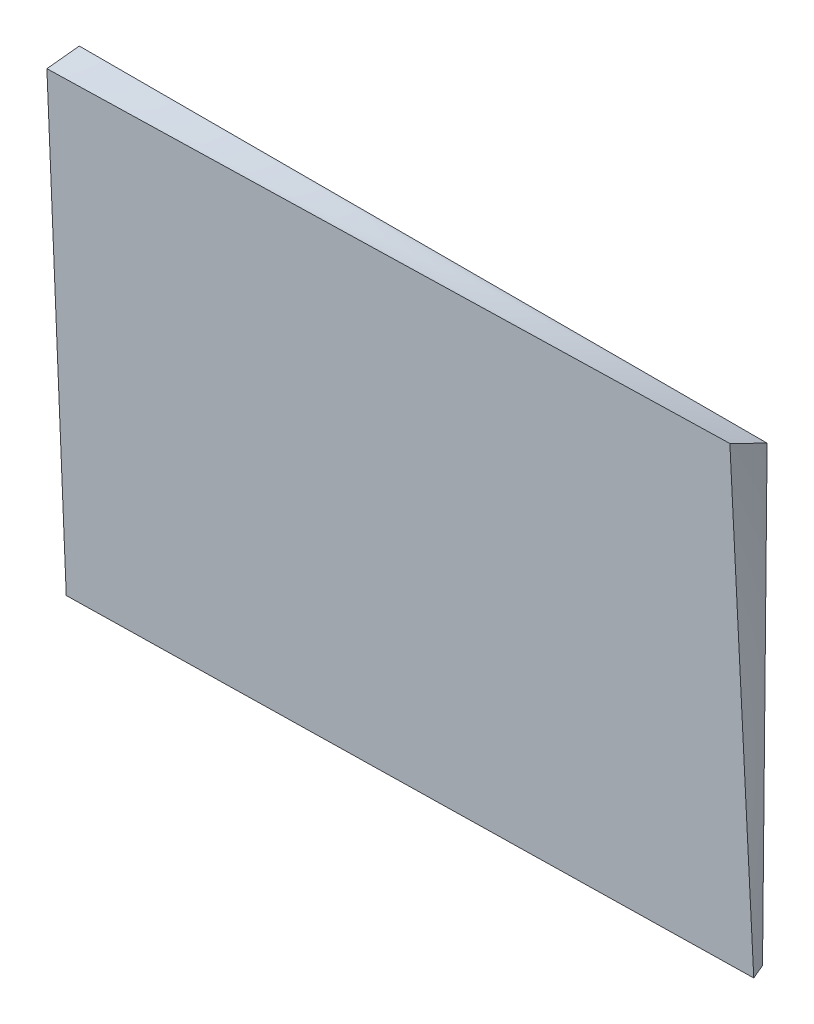
SolidWorks part; units mm, degrees
ref_plane "Ebene vorne" through (0, 0, 0) normal (0, 0, 1) x (1, 0, 0)
ref_plane "Ebene oben" through (0, 0, 0) normal (0, 1, 0) x (1, 0, 0)
ref_plane "Ebene rechts" through (0, 0, 0) normal (1, 0, 0) x (0, 0, -1)
other "Massenmittelpunkt"
sketch "Skizze1" plane through (0, 0, 0) normal (0, 0, 1) x (1, 0, 0)
  line L0 (-14.9998, 9.9997) -> (-14.9998, -10.1003)
  line L1 (-14.9998, -10.1003) -> (14.8995, -9.8992)
  line L2 (14.8995, -9.8992) -> (15.1002, 9.9997)
  line L3 (15.1002, 9.9997) -> (-14.9998, 9.9997)
  line L4 (-14.9998, -0.0503) -> (14.9998, 0.0503) construction
  line L5 (0.0502, 9.9997) -> (-0.0502, -9.9997) construction
  point P3 (0.0502, 9.9997)
  point P5 (14.9998, 0.0503)
  point P6 (-0.0502, -9.9997)
  point P7 (-14.9998, -0.0503)
  point P12 (0, 0)
  dimension "D1" = 30.1
  dimension "D2" = 29.9
  dimension "D3" = 20.1
  dimension "D4" = 19.9
  dimension "D5" = 90
ref_axis "Achse1" through (11, 0, 0) along (-1, 0, 0)
ref_plane "Rotation_Plane" through (0, 0, 0) normal (0, 0.0175, -0.9998) x (-1, 0, 0)
ref_plane "Top_Plane" through (0, -0.0175, 0.9998) normal (0, 0.0175, -0.9998) x (-1, 0, 0)
sketch "Skizze2" plane through (0, -0.0175, 0.9998) normal (0, 0.0175, -0.9998) x (-1, 0, 0)
  line L0 (15.2488, 9.6195) -> (14.7486, -10.2742)
  line L1 (14.7486, -10.2742) -> (-15.3463, -9.7166)
  line L2 (-15.3463, -9.7166) -> (-14.6512, 10.3714)
  line L3 (-14.6512, 10.3714) -> (15.2488, 9.6195)
  line L4 (0.2988, 9.9954) -> (-0.2988, -9.9954) construction
  line L5 (14.9987, -0.3274) -> (-14.9987, 0.3274) construction
  line L6 (-0.0502, 9.9982) -> (0.0502, -9.9982) construction
  line L7 (-0.0502, 9.9982) -> (0.0502, -9.9982) construction
  point P0 (0, 0)
  point P6 (0.2988, 9.9954)
  point P7 (-14.9987, 0.3274)
  point P8 (-0.2988, -9.9954)
  point P9 (14.9987, -0.3274)
  point P14 (0, 0)
  dimension "D5" = 90
  dimension "D1" = 19.9
  dimension "D2" = 20.1
  dimension "D3" = 29.9
  dimension "D4" = 30.1
  dimension "D6" = 2
loft "Ausformung2" add profiles "Skizze1", "Skizze2" connector at (-14.9998, -10.1003, 0) connector at (-14.7486, -10.2901, 0.8205)
ref_point "SWASI_Vision_Point_1_T"
ref_point "SWASI_Vision_Point_1_B"
ref_point "SWASI_Vision_Point_2_T"
ref_point "SWASI_Vision_Point_2_B"
ref_point "SWASI_Vision_Point_3_T"
ref_point "SWASI_Vision_Point_3_B"
ref_point "SWASI_Vision_Point_4_T"
ref_point "SWASI_Vision_Point_4_B"
sketch "Skizze3" plane through (0, -0.0175, 0.9998) normal (0, -0.0175, 0.9998) x (1, 0, 0)
  line L0 (-14.9987, -0.3274) -> (14.9987, 0.3274) construction
  line L1 (-0.2988, 9.9954) -> (0.2988, -9.9954) construction
  line L3 (-14, -9) -> (14, -9)
  line L4 (14.6512, 10.3714) -> (-15.2488, 9.6195)
  line L5 (-15.2488, 9.6195) -> (-14.7486, -10.2742)
  line L6 (-14.7486, -10.2742) -> (15.3463, -9.7166)
  line L7 (15.3463, -9.7166) -> (14.6512, 10.3714)
  line L8 (14.6512, 10.3714) -> (-15.2488, 9.6195) construction
  line L9 (-15.2488, 9.6195) -> (-14.7486, -10.2742) construction
  line L10 (-14.7486, -10.2742) -> (15.3463, -9.7166) construction
  line L11 (15.3463, -9.7166) -> (14.6512, 10.3714) construction
  line L12 (-14, -9) -> (-14, 9)
  line L13 (-14, 9) -> (14, 9)
  line L14 (14, -9) -> (14, 9)
  line L15 (-14, -9) -> (14, 9) construction
  line L16 (-14, 9) -> (14, -9) construction
  point P8 (0, 0)
  point P9 (0, 0)
  dimension "D2" = 28
  dimension "D3" = 18
  dimension "D1" = 0
ref_point "SWASI_Laser_1_T"
ref_point "SWASI_Laser_2_T"
ref_point "SWASI_Laser_3_T"
ref_point "SWASI_Laser_4_T"
ref_point "SWASI_Gripping_Point"
sketch "Skizze4" plane through (0, 0, 0) normal (0, 0, -1) x (-1, 0, 0)
  line L1 (14, 9) -> (-14, 9)
  line L2 (14, 9) -> (14, -9)
  line L3 (14, -9) -> (-14, -9)
  line L4 (-14, 9) -> (-14, -9)
  line L5 (14, 9) -> (-14, -9) construction
  line L6 (14, -9) -> (-14, 9) construction
  point P0 (0, 0)
  point P2 (0, 0)
  dimension "D1" = 28
  dimension "D2" = 18
ref_point "SWASI_Laser_1_B"
ref_point "SWASI_Laser_2_B"
ref_point "SWASI_Laser_3_B"
ref_point "SWASI_Laser_4_B"
ref_plane "SWASI_Top_Plane" through (0, -0.0175, 0.9998) normal (0, 0.0175, -0.9998) x (-1, 0, 0)
ref_plane "SWASI_Bottom_Plane" through (0, 0, 0) normal (0, 0, -1) x (-1, 0, 0)
ref_axis "SWASI_Bottom_Axis" through (14.8995, -9.8992, 0) along (-1, -0.0067, 0)
ref_axis "SWASI_Top_Axis" through (15.3463, -9.7326, 0.8303) along (-0.9998, -0.0185, -0.0003)
sketch "Skizze5" plane through (0, 0, 0) normal (0, 0, -1) x (-1, 0, 0)
  line L0 (14.9998, -10.1003) -> (-14.8995, -9.8992) construction
  line L1 (14.9998, -10.1003) -> (-14.8995, -9.8992)
  point P2 (0.0502, -9.9997)
sketch "Skizze6" plane through (0, -0.0175, 0.9998) normal (0, -0.0175, 0.9998) x (1, 0, 0)
  line L0 (15.3463, -9.7166) -> (-14.7486, -10.2742) construction
  point P0 (0.2988, -9.9954)
  point P1 (-12.736, 25.2765)
ref_point "SWASI_Axis_Center_B"
ref_point "SWASI_Axis_Center_T"
ref_plane "SWASI_Axis_T_Plane" through (0.2988, -10.0114, 0.8254) normal (-0.9998, -0.0185, -0.0003) x (-0.0003, 0, 1)
ref_plane "SWASI_Axis_B_Plane" through (-0.0502, -9.9997, 0) normal (-1, -0.0067, 0) x (0, 0, 1)
ref_plane "Bottom_Reference" through (0, 0, 3) normal (0, 0, -1) x (-1, 0, 0)
ref_plane "Top_Reference" through (0, 0.0349, -1.9997) normal (0, -0.0175, 0.9998) x (1, 0, 0)
sketch "Skizze7" plane through (0, 229.1773, 3) normal (0, 0, -1) x (1, 0, 0)
  point P0 (-14.9998, 239.2776)
ref_point "SWASI_Front_Bottom_Reference"
ref_plane "SWASI_Front_Plane_B" through (0.0672, -9.999, 0) normal (-0.0067, 1, 0) x (1, 0.0067, 0.0001)
sketch "Skizze9" plane through (0, 229.1773, 2) normal (0, -0.0175, 0.9998) x (-1, 0, 0)
  point P0 (-15.3463, 238.8939)
ref_point "SWASI_Front_Top_Reference"
ref_plane "SWASI_Front_Plane_T" through (0.1852, -9.996, -0.1745) normal (0.0185, -0.9997, -0.0174) x (-0.9998, -0.0185, 0)
sketch "Skizze10" plane through (0, 0, 0) normal (0, 0, -1) x (-1, 0, 0)
  line L0 (-16.8995, 11.9997) -> (-16.8995, -8.0003) construction
  line L1 (-16.8995, 11.9997) -> (3.1005, 11.9997) construction
  point P2 (-14.8995, -9.8992)
  point P4 (14.9998, 9.9997)
  dimension "D1" = 20
  dimension "D2" = 20
  dimension "D3" = 2
  dimension "D4" = 2
ref_point "Punkt44"
equation "\"Length_1\"= 20.1"
equation "\"Length_2\"= 19.9"
equation "\"Length_3\"= 30.1"
equation "\"Length_4\"= 29.9"
equation "\"D1@Skizze1\"=\"Length_3\""
equation "\"D2@Skizze1\"=\"Length_4\""
equation "\"D3@Skizze1\"=\"Length_1\""
equation "\"D4@Skizze1\"=\"Length_2\""
equation "\"Angle_1\"= 90"
equation "\"Angle_2\"= 90"
equation "\"Plane_Angle\"= 1"
equation "\"D5@Skizze1\"=\"Angle_1\""
equation "\"Plane_Distance\"= 1"
equation "\"Length_1_1\"= 19.9"
equation "\"Length_1_2\"= 20.1"
equation "\"Length_1_3\"= 29.9"
equation "\"Length_1_4\"= 30.1"
equation "\"Angle_3\"= 90"
equation "\"Angle_4\"= 90"
equation "\"D1@Skizze2\"=\"Length_1_1\""
equation "\"D2@Skizze2\"=\"Length_1_2\""
equation "\"D3@Skizze2\"=\"Length_1_3\""
equation "\"D4@Skizze2\"=\"Length_1_4\""
equation "\"D5@Skizze2\"=\"Angle_3\""
equation "\"Angle_Plane_rot\"= 2"
equation "\"D6@Skizze2\"=\"Angle_Plane_rot\""
